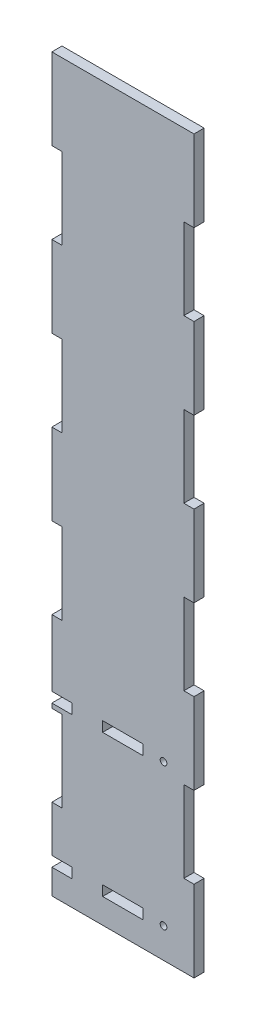
SolidWorks part; units mm, degrees
ref_plane "Front Plane" through (0, 0, 0) normal (0, 0, 1) x (1, 0, 0)
ref_plane "Top Plane" through (0, 0, 0) normal (0, 1, 0) x (1, 0, 0)
ref_plane "Right Plane" through (0, 0, 0) normal (1, 0, 0) x (0, 0, -1)
sketch "Sketch2" plane through (0, 0, 0) normal (0, 1, 0) x (0, 0, 1)
  line L1 (38.1, -44.45) -> (44.45, -44.45)
  line L2 (38.1, -44.45) -> (38.1, 44.45)
  line L3 (38.1, 44.45) -> (44.45, 44.45)
  line L4 (44.45, -44.45) -> (44.45, 44.45)
  dimension "D1" = 88.9
  dimension "D2" = 6.35
extrude "Boss-Extrude1" add sketch "Sketch2" along normal blind 457.2
ref_plane "Plane1" through (0, 0, 0) normal (1, 0, 0) x (0, 0, -1)
sketch "Sketch4" plane through (0, 0, 44.45) normal (0, 0, 1) x (1, 0, 0)
  line L0 (44.45, 457.2) -> (44.45, 406.4) construction
  line L1 (44.45, 457.2) -> (44.45, 0) construction
  line L2 (44.45, 406.4) -> (44.45, 355.6) construction
  line L3 (44.45, 355.6) -> (44.45, 304.8) construction
  line L4 (44.45, 304.8) -> (44.45, 254) construction
  line L5 (44.45, 254) -> (44.45, 203.2) construction
  line L6 (44.45, 203.2) -> (44.45, 152.4) construction
  line L7 (44.45, 152.4) -> (44.45, 101.6) construction
  line L8 (44.45, 101.6) -> (44.45, 50.8) construction
  line L9 (44.45, 50.8) -> (44.45, 0) construction
  line L11 (44.45, 406.4) -> (38.1, 406.4)
  line L12 (44.45, 406.4) -> (44.45, 355.6)
  line L13 (44.45, 355.6) -> (38.1, 355.6)
  line L14 (38.1, 406.4) -> (38.1, 355.6)
  line L15 (44.45, 304.8) -> (38.1, 304.8)
  line L16 (44.45, 304.8) -> (44.45, 254)
  line L17 (44.45, 254) -> (38.1, 254)
  line L18 (38.1, 304.8) -> (38.1, 254)
  line L19 (44.45, 203.2) -> (38.1, 203.2)
  line L20 (44.45, 203.2) -> (44.45, 152.4)
  line L21 (44.45, 152.4) -> (38.1, 152.4)
  line L22 (38.1, 203.2) -> (38.1, 152.4)
  line L23 (44.45, 101.6) -> (38.1, 101.6)
  line L24 (44.45, 101.6) -> (44.45, 50.8)
  line L25 (44.45, 50.8) -> (38.1, 50.8)
  line L26 (38.1, 101.6) -> (38.1, 50.8)
  dimension "D1" = 6.35
extrude "Cut-Extrude1" cut sketch "Sketch4" against normal through all
mirror "Mirror1" about plane through (0, 0, 0) normal (1, 0, 0) of "Cut-Extrude1"
sketch "Sketch5" plane through (0, 0, 38.1) normal (0, 0, -1) x (-1, 0, 0)
  line L0 (0, 0) -> (0, 124.5607) construction
  line L1 (-12.7, 110.8375) -> (12.7, 110.8375)
  line L2 (-12.7, 110.8375) -> (-12.7, 104.4875)
  line L3 (-12.7, 104.4875) -> (12.7, 104.4875)
  line L4 (12.7, 110.8375) -> (12.7, 104.4875)
  line L5 (-12.7, 21.9375) -> (12.7, 21.9375)
  line L6 (-12.7, 21.9375) -> (-12.7, 15.5875)
  line L7 (-12.7, 15.5875) -> (12.7, 15.5875)
  line L8 (12.7, 21.9375) -> (12.7, 15.5875)
  line L36 (38.1, 101.6) -> (44.45, 101.6)
  line L37 (44.45, 101.6) -> (44.45, 152.4)
  line L38 (44.45, 152.4) -> (38.1, 152.4)
  line L39 (38.1, 152.4) -> (38.1, 203.2)
  line L40 (38.1, 203.2) -> (44.45, 203.2)
  line L41 (44.45, 203.2) -> (44.45, 254)
  line L42 (44.45, 254) -> (38.1, 254)
  line L43 (38.1, 254) -> (38.1, 304.8)
  line L44 (38.1, 304.8) -> (44.45, 304.8)
  line L45 (44.45, 304.8) -> (44.45, 355.6)
  line L46 (44.45, 355.6) -> (38.1, 355.6)
  line L47 (38.1, 355.6) -> (38.1, 406.4)
  line L48 (38.1, 406.4) -> (44.45, 406.4)
  line L49 (44.45, 406.4) -> (44.45, 457.2)
  line L50 (44.45, 457.2) -> (-44.45, 457.2)
  line L51 (-44.45, 457.2) -> (-44.45, 406.4)
  line L52 (-44.45, 406.4) -> (-38.1, 406.4)
  line L53 (-38.1, 406.4) -> (-38.1, 355.6)
  line L54 (-38.1, 355.6) -> (-44.45, 355.6)
  line L55 (-44.45, 355.6) -> (-44.45, 304.8)
  line L56 (-44.45, 304.8) -> (-38.1, 304.8)
  line L57 (-38.1, 304.8) -> (-38.1, 254)
  line L58 (-38.1, 254) -> (-44.45, 254)
  line L59 (-44.45, 254) -> (-44.45, 203.2)
  line L60 (-44.45, 203.2) -> (-38.1, 203.2)
  line L61 (-38.1, 203.2) -> (-38.1, 152.4)
  line L62 (-38.1, 152.4) -> (-44.45, 152.4)
  line L63 (-44.45, 152.4) -> (-44.45, 101.6)
  line L64 (-44.45, 101.6) -> (-38.1, 101.6)
  line L65 (-38.1, 101.6) -> (-38.1, 50.8)
  line L66 (-38.1, 50.8) -> (-44.45, 50.8)
  line L67 (-44.45, 50.8) -> (-44.45, 0)
  line L68 (-44.45, 0) -> (44.45, 0)
  line L69 (44.45, 0) -> (44.45, 50.8)
  line L70 (44.45, 50.8) -> (38.1, 50.8)
  line L71 (38.1, 50.8) -> (38.1, 101.6)
  line L72 (38.1, 101.6) -> (44.45, 101.6)
  line L73 (44.45, 101.6) -> (44.45, 152.4)
  line L74 (44.45, 152.4) -> (38.1, 152.4)
  line L75 (38.1, 152.4) -> (38.1, 203.2)
  line L76 (38.1, 203.2) -> (44.45, 203.2)
  line L77 (44.45, 203.2) -> (44.45, 254)
  line L78 (44.45, 254) -> (38.1, 254)
  line L79 (38.1, 254) -> (38.1, 304.8)
  line L80 (38.1, 304.8) -> (44.45, 304.8)
  line L81 (44.45, 304.8) -> (44.45, 355.6)
  line L82 (44.45, 355.6) -> (38.1, 355.6)
  line L83 (38.1, 355.6) -> (38.1, 406.4)
  line L84 (38.1, 406.4) -> (44.45, 406.4)
  line L85 (44.45, 406.4) -> (44.45, 457.2)
  line L86 (44.45, 457.2) -> (-44.45, 457.2)
  line L87 (-44.45, 457.2) -> (-44.45, 406.4)
  line L88 (-44.45, 406.4) -> (-38.1, 406.4)
  line L89 (-38.1, 406.4) -> (-38.1, 355.6)
  line L90 (-38.1, 355.6) -> (-44.45, 355.6)
  line L91 (-44.45, 355.6) -> (-44.45, 304.8)
  line L92 (-44.45, 304.8) -> (-38.1, 304.8)
  line L93 (-38.1, 304.8) -> (-38.1, 254)
  line L94 (-38.1, 254) -> (-44.45, 254)
  line L95 (-44.45, 254) -> (-44.45, 203.2)
  line L96 (-44.45, 203.2) -> (-38.1, 203.2)
  line L97 (-38.1, 203.2) -> (-38.1, 152.4)
  line L98 (-38.1, 152.4) -> (-44.45, 152.4)
  line L99 (-44.45, 152.4) -> (-44.45, 101.6)
  line L100 (-44.45, 101.6) -> (-38.1, 101.6)
  line L101 (-38.1, 101.6) -> (-38.1, 50.8)
  line L102 (-38.1, 50.8) -> (-44.45, 50.8)
  line L103 (-44.45, 50.8) -> (-44.45, 0)
  line L104 (-44.45, 0) -> (44.45, 0)
  line L105 (44.45, 0) -> (44.45, 50.8)
  line L106 (44.45, 50.8) -> (38.1, 50.8)
  line L107 (38.1, 50.8) -> (38.1, 101.6)
  dimension "D2" = 6.35
  dimension "D3" = 6.35
  dimension "D4" = 25.4
  dimension "D5" = 25.4
  dimension "D6" = 82.55
  dimension "D7" = 15.5875
  dimension "D1" = 0
extrude "Cut-Extrude2" cut sketch "Sketch5" against normal through all contours L0 L7 L8 L5 | L7 L0 L5 L6 | L0 L3 L4 L1 | L3 L0 L1 L2 region at (6.35, 107.6625, 38.1) region at (-6.35, 107.6625, 38.1) region at (6.35, 18.7625, 38.1) region at (-6.35, 18.7625, 38.1)
sketch "Sketch6" plane through (0, 0, 44.45) normal (0, 0, 1) x (1, 0, 0)
  line L0 (25.4, 107.6625) -> (-25.4, 107.6625) construction
  line L1 (12.7, 110.8375) -> (-12.7, 110.8375) construction
  line L2 (12.7, 104.4875) -> (-12.7, 104.4875) construction
  line L3 (-25.4, 18.7625) -> (25.4, 18.7625) construction
  line L4 (12.7, 21.9375) -> (-12.7, 21.9375) construction
  line L5 (12.7, 15.5875) -> (-12.7, 15.5875) construction
  line L6 (0, 132.4794) -> (0, 71.8673) construction
  line L7 (-12.7, 110.8375) -> (-12.7, 104.4875) construction
  line L8 (12.7, 110.8375) -> (12.7, 104.4875) construction
  circle A0 centre (25.4, 107.6625) radius 2.0955
  circle A3 centre (25.4, 18.7625) radius 2.0955
  dimension "D1" = 4.191
  dimension "D2" = 12.7
extrude "Cut-Extrude3" cut sketch "Sketch6" against normal through all
sketch "Sketch7" plane through (0, 0, 38.1) normal (0, 0, -1) x (-1, 0, 0)
  line L0 (44.45, 152.4) -> (44.45, 101.6) construction
  line L1 (31.75, 110.8375) -> (44.45, 110.8375)
  line L2 (31.75, 110.8375) -> (31.75, 104.4875)
  line L3 (31.75, 104.4875) -> (44.45, 104.4875)
  line L4 (44.45, 110.8375) -> (44.45, 104.4875)
extrude "Cut-Extrude4" cut sketch "Sketch7" against normal blind 10
sketch "Sketch8" plane through (0, 0, 38.1) normal (0, 0, -1) x (-1, 0, 0)
  line L0 (44.45, 50.8) -> (44.45, 0) construction
  line L1 (31.75, 21.9375) -> (44.45, 21.9375)
  line L2 (31.75, 21.9375) -> (31.75, 15.5875)
  line L3 (31.75, 15.5875) -> (44.45, 15.5875)
  line L4 (44.45, 21.9375) -> (44.45, 15.5875)
extrude "Cut-Extrude5" cut sketch "Sketch8" against normal through all
